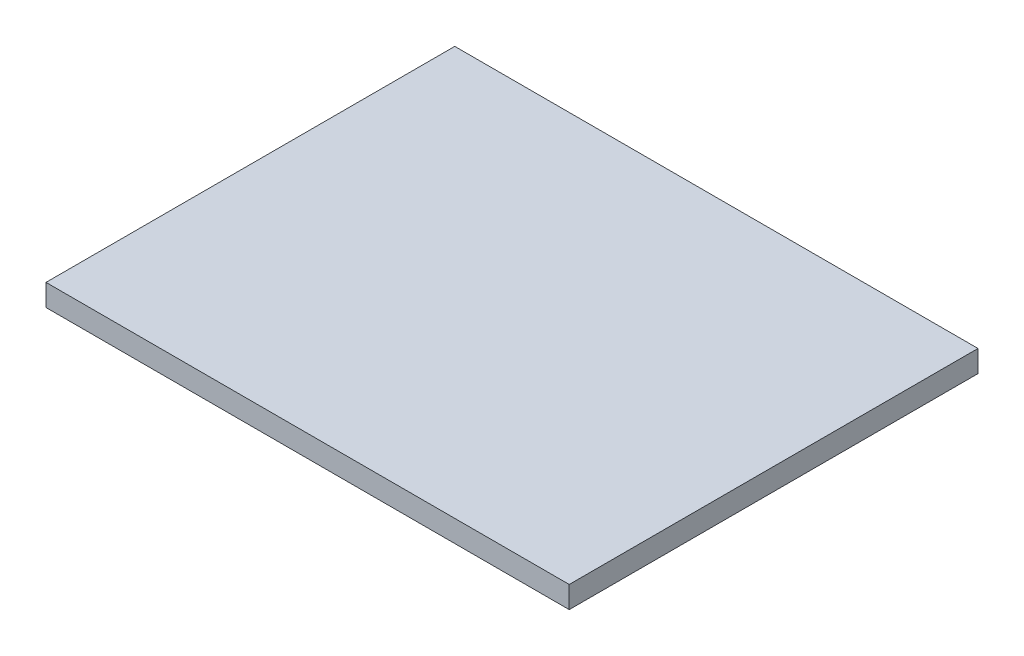
SolidWorks part; units mm, degrees
ref_plane "Front Plane" through (0, 0, 0) normal (0, 0, 1) x (1, 0, 0)
ref_plane "Top Plane" through (0, 0, 0) normal (0, 1, 0) x (1, 0, 0)
ref_plane "Right Plane" through (0, 0, 0) normal (1, 0, 0) x (0, 0, -1)
ref_plane "Plane1" through (0, 72.59, 0) normal (0, 1, 0) x (1, 0, 0)
sketch "Sketch1" plane through (0, 72.59, 0) normal (0, 1, 0) x (1, 0, 0)
  line L1 (98, 75) -> (2, 75)
  line L2 (98, 75) -> (98, 0)
  line L3 (98, 0) -> (2, 0)
  line L4 (2, 75) -> (2, 0)
extrude "Boss-Extrude1" add sketch "Sketch1" against normal blind 4
